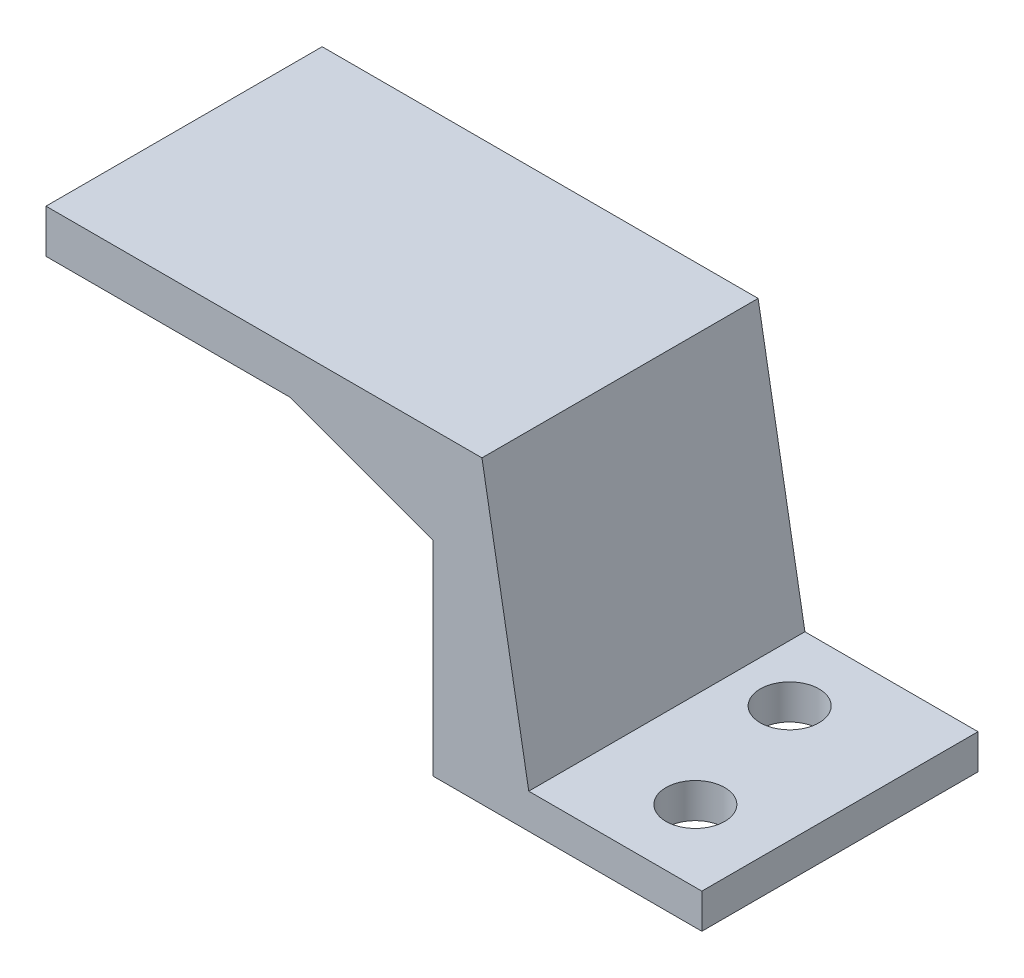
SolidWorks part; units mm, degrees
material "ABS"
ref_plane "Front Plane" through (0, 0, 0) normal (0, 0, 1) x (1, 0, 0)
ref_plane "Top Plane" through (0, 0, 0) normal (0, 1, 0) x (1, 0, 0)
ref_plane "Right Plane" through (0, 0, 0) normal (1, 0, 0) x (0, 0, -1)
sketch "Sketch1" plane through (0, 0, 0) normal (0, 0, 1) x (1, 0, 0)
  line L0 (0, 0) -> (0, 29.5)
  line L1 (0, 29.5) -> (5.5, 29.5)
  line L2 (5.5, 29.5) -> (5.5, 4)
  line L3 (5.5, 4) -> (30.9, 4)
  line L4 (30.9, 4) -> (30.9, 0)
  line L5 (30.9, 0) -> (0, 0)
  line L7 (5.5, 29.5) -> (-44.5, 29.5)
  line L8 (5.5, 29.5) -> (5.5, 34.5)
  line L9 (5.5, 34.5) -> (-44.5, 34.5)
  line L10 (-44.5, 29.5) -> (-44.5, 34.5)
  line L11 (5.5, 29.5) -> (-44.5, 34.5) construction
  line L12 (5.5, 34.5) -> (-44.5, 29.5) construction
  point P10 (-19.5, 32)
  dimension "D1" = 4
  dimension "D2" = 25.4
  dimension "D3" = 25.5
  dimension "D4" = 5
  dimension "D5" = 50
  dimension "D6" = 5.5
extrude "Boss-Extrude1" add sketch "Sketch1" along normal blind 31.75 contours L5 L4 L3 L2 L1 L0 | L10 L7 L1 L8 L9 region at (0.4272, 14.75, 0) region at (-19.5, 32, 0)
hole_wizard "1/4 Clearance Hole1" positions "Sketch2" profile "Sketch3" hole size "1/4" standard "ANSI Inch" end condition through all
sketch "Sketch2" plane through (0, 4, 0) normal (0, 1, 0) x (1, 0, 0)
  line L0 (5.5, -31.75) -> (5.5, 0) construction
  line L1 (30.9, -31.75) -> (30.9, 0) construction
  point P0 (21.9, -23.495)
  point P2 (17.5, -8.255)
  point P10 (30.9, -15.875)
  dimension "D1" = 16.4
  dimension "D2" = 12
  dimension "D3" = 15.24
  dimension "D4" = 7.62
sketch "Sketch3" plane through (21.9, 4, 23.495) normal (1, 0, 0) x (0, 0, 1)
  line L0 (0, 0) -> (0, 4)
  line L1 (0, 4) -> (3.3782, 4)
  line L2 (3.3782, 4) -> (3.3782, 0)
  line L5 (3.3782, 0) -> (0, 0)
  line L11 (0, -6.35) -> (0, 107.95) construction
  dimension "Thru Hole Dia." = 6.7564
  dimension "Thru Hole Depth" = 4
chamfer "Chamfer1" distance 5.5 angle 80 1 edges at (5.5, 4, 15.875) first distance on face at (21.9, 4, 26.8732)
chamfer "Chamfer2" distance 6 angle 70 1 edges at (0, 29.5, 15.875) first distance on face at (0, 14.75, 15.875)
equation "\"D4@Sketch2\"=\"D3@Sketch2\"/2"
